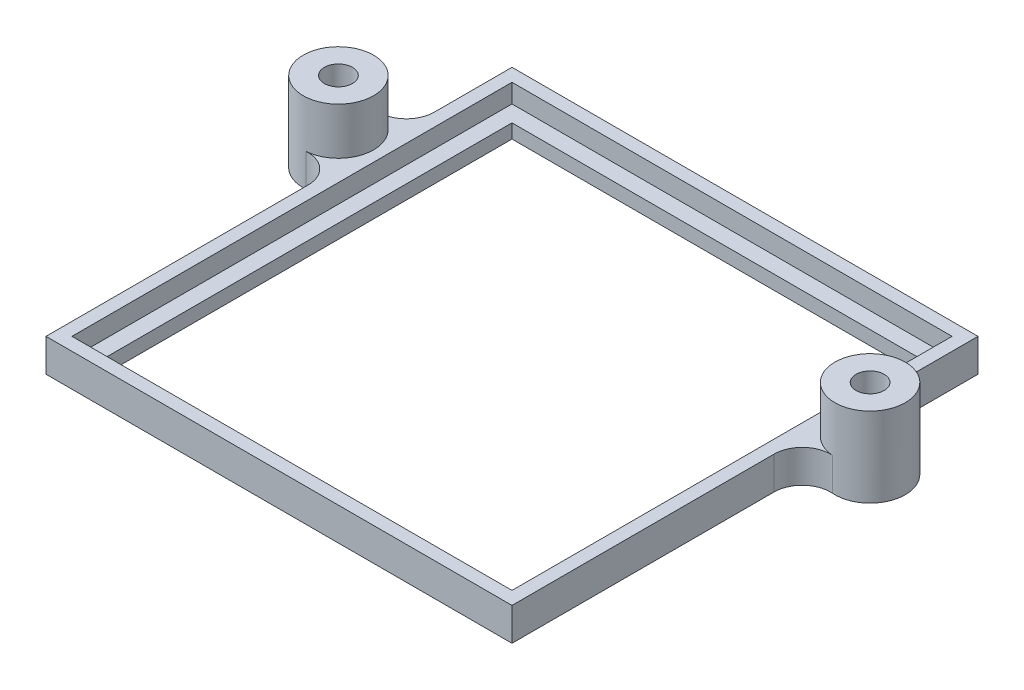
SolidWorks part; units mm, degrees
ref_plane "Front Plane" through (0, 0, 0) normal (0, 0, 1) x (1, 0, 0)
ref_plane "Top Plane" through (0, 0, 0) normal (0, 1, 0) x (1, 0, 0)
ref_plane "Right Plane" through (0, 0, 0) normal (1, 0, 0) x (0, 0, -1)
sketch "Sketch1" plane through (0, 0, 0) normal (0, 1, 0) x (1, 0, 0)
  line L0 (0, 38.3713) -> (0, 0) construction
  line L1 (-22.5, -22.5) -> (22.5, -22.5) construction
  line L2 (-22.5, -22.5) -> (-22.5, 22.5) construction
  line L3 (-22.5, 22.5) -> (22.5, 22.5) construction
  line L4 (22.5, -22.5) -> (22.5, 22.5) construction
  line L5 (-22.5, -22.5) -> (22.5, 22.5) construction
  line L6 (-22.5, 22.5) -> (22.5, -22.5) construction
  line L7 (-21.7061, -21.7061) -> (21.7061, -21.7061)
  line L8 (-21.7061, -21.7061) -> (-21.7061, 21.7061)
  line L9 (-21.7061, 21.7061) -> (21.7061, 21.7061)
  line L10 (21.7061, -21.7061) -> (21.7061, 21.7061)
  line L11 (-21.7061, -21.7061) -> (21.7061, 21.7061) construction
  line L12 (-21.7061, 21.7061) -> (21.7061, -21.7061) construction
  line L13 (-23.4483, -23.4483) -> (23.4483, -23.4483)
  line L14 (-23.4483, -23.4483) -> (-23.4483, 23.4483)
  line L15 (-23.4483, 23.4483) -> (23.4483, 23.4483)
  line L16 (23.4483, -23.4483) -> (23.4483, 23.4483)
  line L17 (-23.4483, -23.4483) -> (23.4483, 23.4483) construction
  line L18 (-23.4483, 23.4483) -> (23.4483, -23.4483) construction
  line L19 (-24.8321, -24.8321) -> (24.8321, -24.8321)
  line L20 (-24.8321, -24.8321) -> (-24.8321, 24.8321)
  line L21 (-24.8321, 24.8321) -> (24.8321, 24.8321)
  line L22 (24.8321, -24.8321) -> (24.8321, 24.8321)
  line L23 (-24.8321, -24.8321) -> (24.8321, 24.8321) construction
  line L24 (-24.8321, 24.8321) -> (24.8321, -24.8321) construction
  line L25 (0, 0) -> (46.6292, 0) construction
  point P0 (0, 0)
  point P6 (0, 0)
  point P11 (0, 0)
  point P16 (0, 0)
  dimension "D1" = 45
  dimension "D2" = 45
extrude "Boss-Extrude1" add sketch "Sketch1" along normal blind 1.5 contours L13 L16 L15 L14 L10 L7 L8 L9 region at (-22.785, 0, 0)
extrude "Boss-Extrude2" add sketch "Sketch1<3>" along normal blind 3.5 contours L19 L22 L21 L20 L16 L13 L14 L15 region at (-24.1298, 0, 0)
sketch "Sketch1<3>" plane through (0, 0, 0) normal (0, 1, 0) x (1, 0, 0) same geometry as "Sketch1"
sketch "Sketch2" plane through (0, 3.5, 0) normal (0, 1, 0) x (1, 0, 0)
  line L0 (-36.1753, 9.8321) -> (31.7444, 9.8321) construction
  line L1 (-24.8321, 24.8321) -> (24.8321, 24.8321) construction
  line L2 (-24.8321, -24.8321) -> (-24.8321, 24.8321) construction
  line L3 (0, 0) -> (0, 18.2846) construction
  circle A0 centre (-28.3321, 9.8321) radius 1.5
  circle A1 centre (-28.3321, 9.8321) radius 3.75
  circle A2 centre (28.3321, 9.8321) radius 1.5
  circle A3 centre (28.3321, 9.8321) radius 3.75
  dimension "D2" = 3
  dimension "D3" = 7.5
  dimension "D5" = 56.6643
  dimension "D1" = 15
  dimension "D4" = 3.5
extrude "Boss-Extrude4" add sketch "Sketch2" along normal blind 5 and the other way up to surface (3.5 mm away) other way up to face at (0, 0, 0)
fillet "Fillet2" radius 3 4 edges at (-24.8321, 1.75, -8.4858) (-24.8321, 1.75, -11.1784) (24.8321, 1.75, -11.1784) (24.8321, 1.75, -8.4858)
